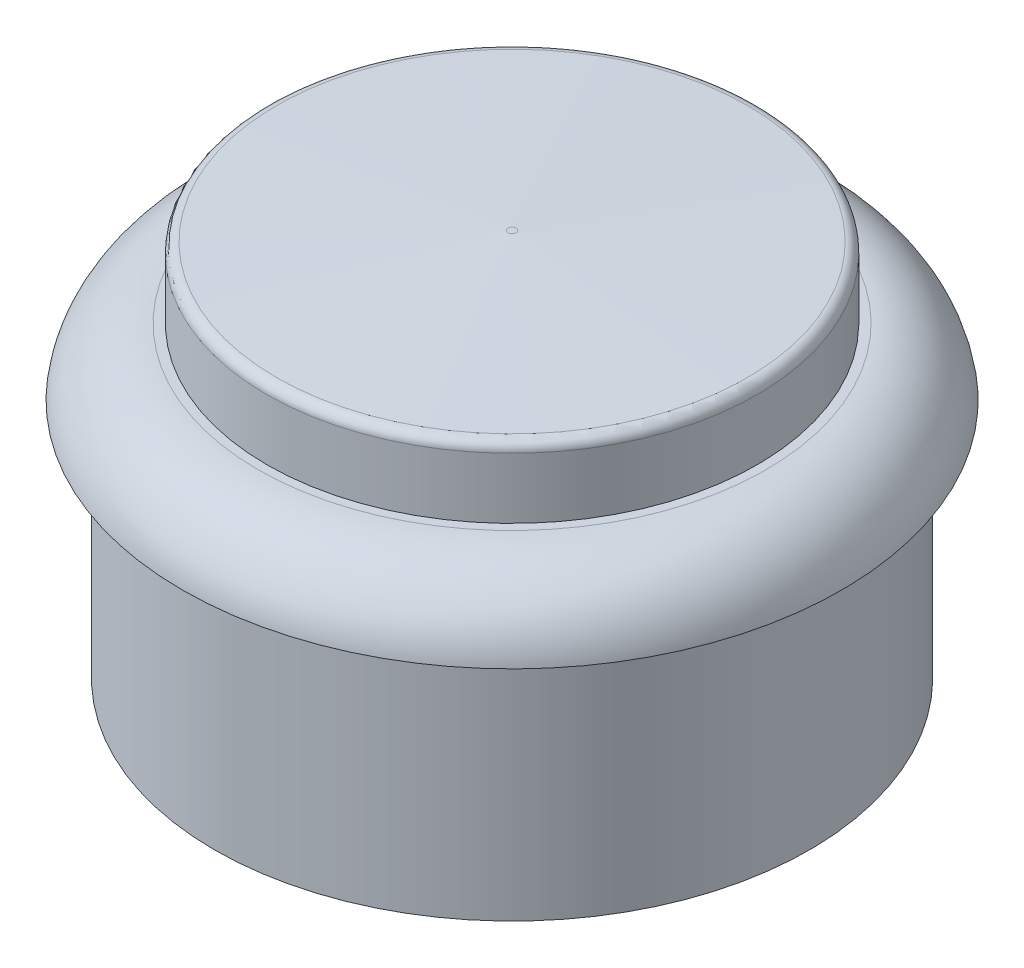
SolidWorks part; units mm, degrees
ref_plane "Front Plane" through (0, 0, 0) normal (0, 0, 1) x (1, 0, 0)
ref_plane "Top Plane" through (0, 0, 0) normal (0, 1, 0) x (1, 0, 0)
ref_plane "Right Plane" through (0, 0, 0) normal (1, 0, 0) x (0, 0, -1)
sketch "Sketch1" plane through (0, 0, 0) normal (0, 1, 0) x (1, 0, 0)
  circle A0 centre (0, 0) radius 14.8
  dimension "D1" = 29.6
extrude "Boss-Extrude1" add sketch "Sketch1" along normal blind 12
sketch "Sketch2" plane through (0, 12, 0) normal (0, 1, 0) x (1, 0, 0)
  circle A0 centre (0, 0) radius 16.4
  dimension "D1" = 32.8
extrude "Boss-Extrude2" add sketch "Sketch2" along normal blind 3.3
fillet "Fillet1" radius 3.8 1 edges at (0, 15.3, 16.4)
sketch "Sketch3" plane through (0, 15.3, 0) normal (0, 1, 0) x (1, 0, 0)
  circle A0 centre (0, 0) radius 12.2
  dimension "D1" = 24.4
extrude "Boss-Extrude3" add sketch "Sketch3" along normal blind 4
chamfer "Chamfer1" distance 0.5 distance2 12 1 edges at (0, 19.3, 12.2) first distance on face at (0, 19.3, 12.2)
fillet "Fillet2" radius 0.5 1 edges at (0, 18.8, 12.2)
